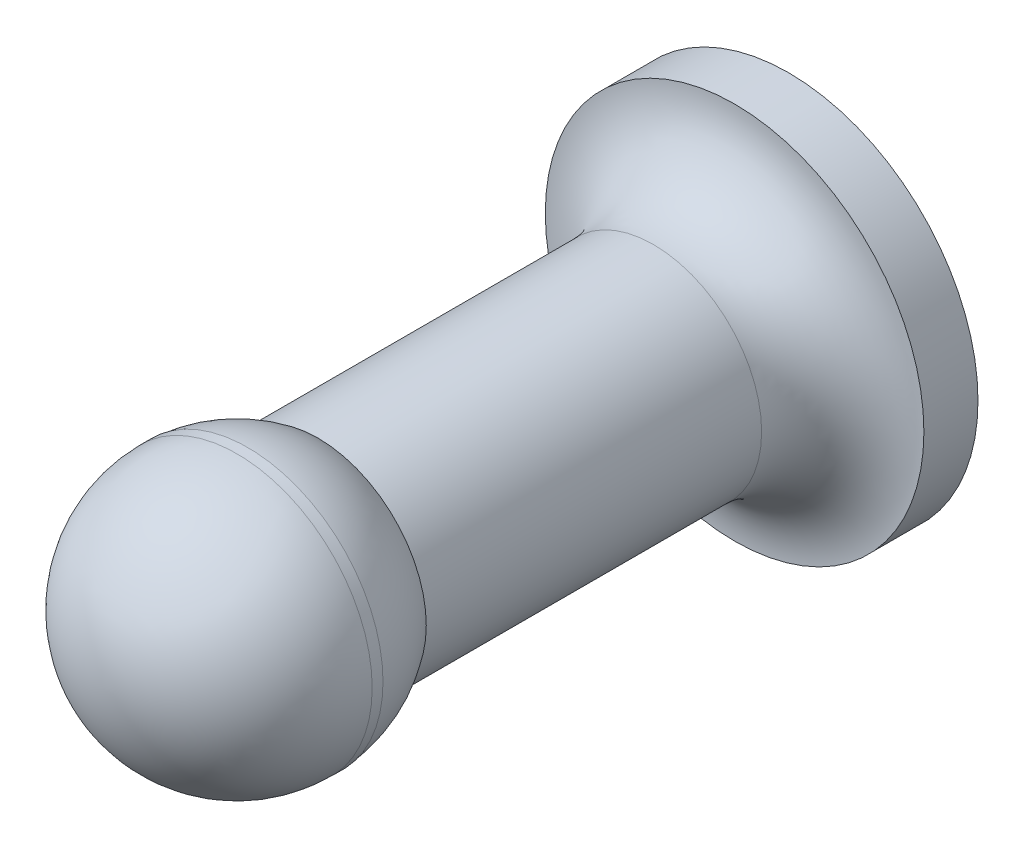
SolidWorks part; units mm, degrees
material "AISI 304"
ref_plane "Front Plane" through (0, 0, 0) normal (0, 0, 1) x (1, 0, 0)
ref_plane "Top Plane" through (0, 0, 0) normal (0, 1, 0) x (1, 0, 0)
ref_plane "Right Plane" through (0, 0, 0) normal (1, 0, 0) x (0, 0, -1)
sketch "Sketch1" plane through (0, 0, 0) normal (0, 0, 1) x (1, 0, 0)
  circle A0 centre (0, 0) radius 17.5
  dimension "D1" = 35
extrude "Boss-Extrude1" add sketch "Sketch1" along normal blind 5
sketch "Sketch3" plane through (0, 0, 0) normal (0, 0, 1) x (1, 0, 0)
  circle A0 centre (0, 0) radius 10
  dimension "D1" = 20
extrude "Boss-Extrude2" add sketch "Sketch3" along normal blind 50 contours A0
sketch "Sketch6" plane through (0, 0, 50) normal (0, 0, 1) x (1, 0, 0)
  circle A1 centre (0, 0) radius 12.5
  dimension "D1" = 25
extrude "Boss-Extrude3" add sketch "Sketch6" along normal blind 1 contours A1
sketch "Sketch7" plane through (0, 0, 51) normal (0, 0, 1) x (1, 0, 0)
  line L0 (0, 12.5) -> (0, -12.5)
  arc A0 (0, 12.5) -> (0, -12.5) centre (0, 0) ccw
  circle A1 centre (0, 0) radius 12.5 construction
revolve "Revolve5" add sketch "Sketch7" angle 360 about L0
fillet "Fillet1" radius 7.5 1 edges at (10, 0, 5)
